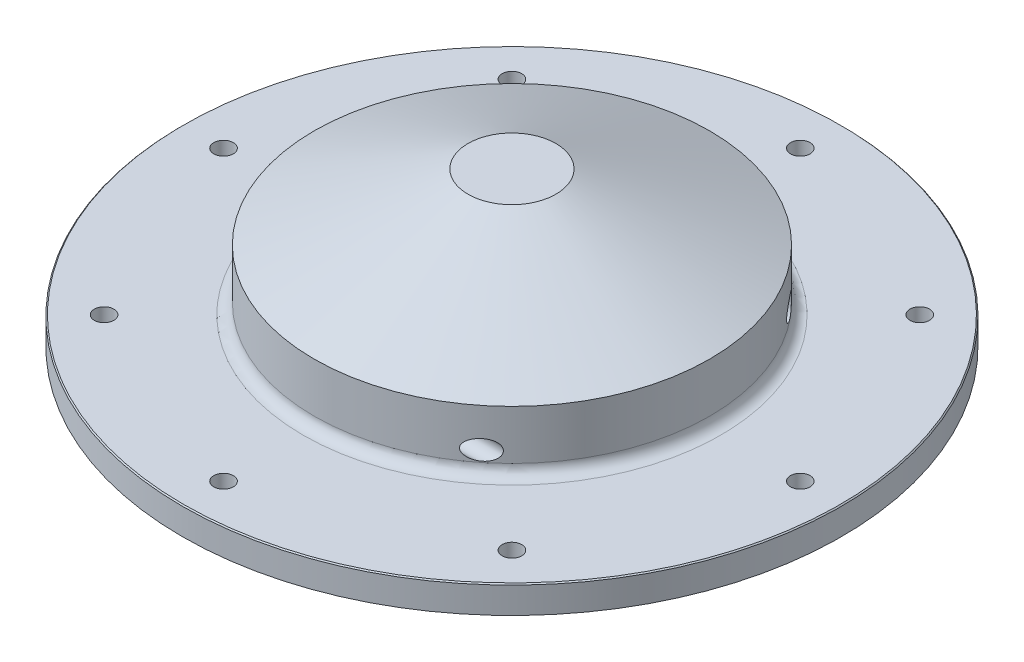
SolidWorks part; units mm, degrees
ref_plane "Front Plane" through (0, 0, 0) normal (0, 0, 1) x (1, 0, 0)
ref_plane "Top Plane" through (0, 0, 0) normal (0, 1, 0) x (1, 0, 0)
ref_plane "Right Plane" through (0, 0, 0) normal (1, 0, 0) x (0, 0, -1)
sketch "Sketch2" plane through (0, 0, 0) normal (0, 1, 0) x (1, 0, 0)
  circle A0 centre (0, 0) radius 38.1
  dimension "D1" = 76.2
extrude "Boss-Extrude1" add sketch "Sketch2" along normal blind 3.175
hole_wizard "Tap Drill for #4-40 Tap1" positions "Sketch3" profile "Sketch4" hole size "#4-40" standard "ANSI Inch" end condition through all
sketch "Sketch3" plane through (0, 0, 0) normal (0, -1, 0) x (-1, 0, 0)
  point P0 (0, -33.3375)
  dimension "D1" = 33.3375
sketch "Sketch4" plane through (0, 0, 33.3375) normal (1, 0, 0) x (0, 0, -1)
  line L0 (0, 0) -> (0, 3.175)
  line L1 (0, 3.175) -> (1.1303, 3.175)
  line L2 (1.1303, 3.175) -> (1.1303, 0)
  line L5 (1.1303, 0) -> (0, 0)
  line L11 (0, -6.35) -> (0, 107.95) construction
  dimension "Thru Hole Dia." = 2.2606
  dimension "Thru Hole Depth" = 3.175
pattern_circular "CirPattern1" count 8 over 360 about axis through (0, 0, 0) along (0, 1, 0) of "Tap Drill for #4-40 Tap1"
sketch "Sketch5" plane through (0, 3.175, 0) normal (0, 1, 0) x (1, 0, 0)
  circle A0 centre (0, 0) radius 28.575
  dimension "D1" = 57.15
sketch "Sketch7" plane through (0, 3.175, 0) normal (0, 1, 0) x (1, 0, 0)
  circle A0 centre (0, 0) radius 22.86
  dimension "D1" = 45.72
extrude "Boss-Extrude2" add sketch "Sketch7" along normal blind 6.985
sketch "Sketch8" plane through (0, 0, 0) normal (0, -1, 0) x (1, 0, 0)
  circle A0 centre (0, 0) radius 19.05
  dimension "D1" = 38.1
extrude "Cut-Extrude1" cut sketch "Sketch8" against normal blind 8.255
hole_wizard "Tap Drill for #4-40 Tap2" positions "Sketch11" profile "Sketch12" hole size "#4-40" standard "ANSI Inch" end condition through all
sketch "Sketch11" plane through (0, 0, 0) normal (0, 0, 1) x (1, 0, 0)
  line L0 (0, -1.7463) -> (0, 1.7463) construction
  line L1 (22.86, 3.175) -> (-22.86, 3.175) construction
  point P0 (-17.78, 5.715)
  dimension "D1" = 17.78
  dimension "D2" = 2.54
sketch "Sketch12" plane through (-17.78, 5.715, 0) normal (1, 0, 0) x (0, 1, 0)
  line L0 (0, 0) -> (0, 38.1)
  line L1 (0, 38.1) -> (1.1303, 38.1)
  line L2 (1.1303, 38.1) -> (1.1303, 0)
  line L5 (1.1303, 0) -> (0, 0)
  line L11 (0, -6.35) -> (0, 107.95) construction
  dimension "Thru Hole Dia." = 2.2606
  dimension "Thru Hole Depth" = 38.1
pattern_circular "CirPattern2" count 4 over 360 about axis through (0, 10.16, 0) along (0, 1, 0) of "Tap Drill for #4-40 Tap2"
sketch "Sketch13" plane through (0, 10.16, 0) normal (0, 1, 0) x (1, 0, 0)
  circle A0 centre (0, 0) radius 22.86
  circle A1 centre (0, 0) radius 22.86 construction
  dimension "D1" = 0
ref_plane "Plane2" through (0, 17.78, 0) normal (0, 1, 0) x (1, 0, 0)
sketch "Sketch14" plane through (0, 17.78, 0) normal (0, 1, 0) x (1, 0, 0)
  circle A0 centre (0, 0) radius 5.08
  dimension "D1" = 10.16
loft "Loft2" add profiles "Sketch14", "Sketch13" connector at (-0.0647, 17.78, 5.0796) connector at (0, 10.16, 22.86)
fillet "Fillet1" radius 0.635 1 edges at (0, 8.255, -19.05)
chamfer "Chamfer1" distance 0.127 angle 45 1 edges at (0, 3.175, 38.1)
fillet "Fillet2" radius 1.27 1 edges at (0, 3.175, 22.86)
